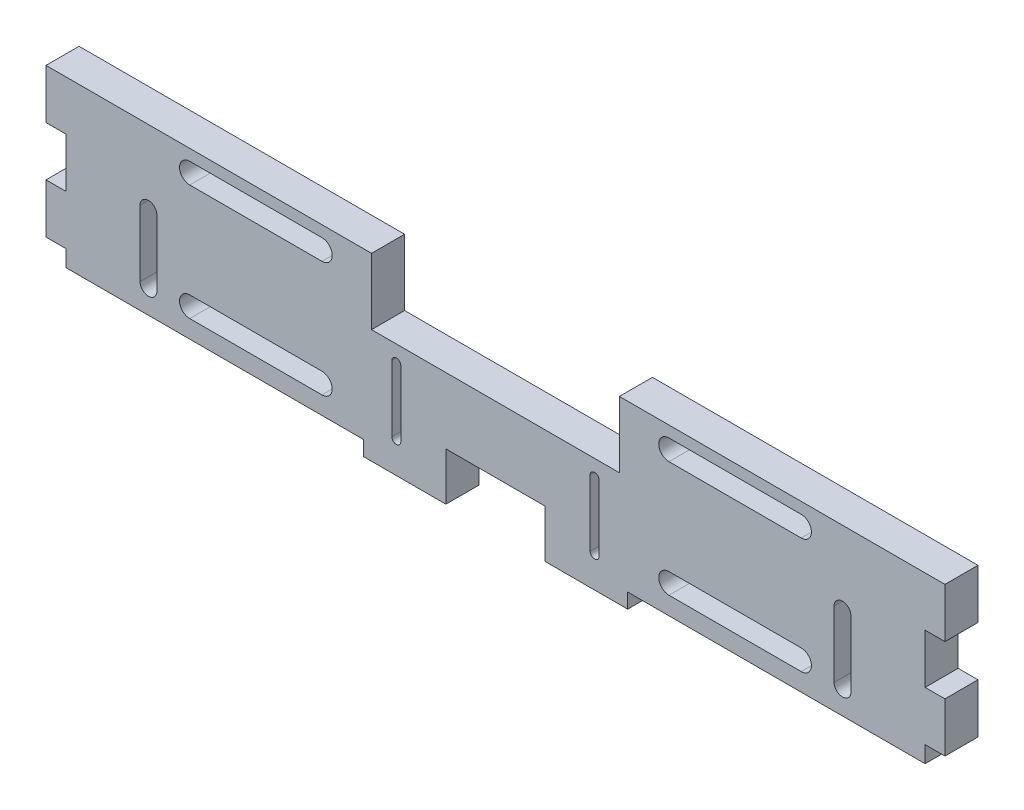
SolidWorks part; units mm, degrees
ref_plane "前基準面" through (0, 0, 0) normal (0, 0, 1) x (1, 0, 0)
ref_plane "上基準面" through (0, 0, 0) normal (0, 1, 0) x (1, 0, 0)
ref_plane "右基準面" through (0, 0, 0) normal (1, 0, 0) x (0, 0, -1)
sketch "草圖1" plane through (0, 0, 0) normal (0, 0, 1) x (1, 0, 0)
  line L0 (136, -22.5) -> (136, -7.5)
  line L1 (136, 22.5) -> (-136, 22.5)
  line L2 (130, 7.5) -> (130, -7.5)
  line L3 (130, -27.5) -> (-130, -27.5)
  line L4 (-130, 7.5) -> (-130, -7.5)
  line L5 (0, -27.5) -> (0, 22.5) construction
  line L6 (130, 0) -> (-130, 0) construction
  line L9 (-130, 7.5) -> (-136, 7.5)
  line L10 (-136, 22.5) -> (-136, 7.5)
  line L14 (-136, -22.5) -> (-136, -7.5)
  line L15 (130, -7.5) -> (136, -7.5)
  line L16 (130, 7.5) -> (136, 7.5)
  line L17 (136, 22.5) -> (136, 7.5)
  line L18 (-136, -22.5) -> (-130, -22.5)
  line L19 (-130, -22.5) -> (-130, -27.5)
  line L20 (-136, -7.5) -> (-130, -7.5)
  line L21 (130, -22.5) -> (130, -27.5)
  line L22 (130, -22.5) -> (136, -22.5)
  line L23 (-30, -22.5) -> (-30, -2.5) construction
  line L24 (-31.35, -22.5) -> (-31.35, -2.5)
  line L25 (-28.65, -22.5) -> (-28.65, -2.5)
  line L26 (30, -22.5) -> (30, -2.5) construction
  line L27 (31.35, -22.5) -> (31.35, -2.5)
  line L28 (28.65, -22.5) -> (28.65, -2.5)
  arc A0 (-31.35, -22.5) -> (-28.65, -22.5) centre (-30, -22.5) ccw
  arc A1 (-28.65, -2.5) -> (-31.35, -2.5) centre (-30, -2.5) ccw
  arc A2 (31.35, -22.5) -> (28.65, -22.5) centre (30, -22.5) cw
  arc A3 (28.65, -2.5) -> (31.35, -2.5) centre (30, -2.5) cw
  point P0 (0, 0)
  point P8 (0, 0)
  point P13 (-136, -15)
  point P14 (136, -15)
  point P24 (-30, -12.5)
  point P31 (30, -12.5)
  dimension "D8" = 1.35
  dimension "D1" = 260
  dimension "D2" = 6
  dimension "D3" = 15
  dimension "D4" = 6
  dimension "D5" = 50
  dimension "D6" = 5
  dimension "D7" = 20
  dimension "D9" = 5
  dimension "D10" = 30
extrude "填料-伸長1" add sketch "草圖1" along normal blind 10
sketch "草圖2" plane through (0, 0, 10) normal (0, 0, 1) x (1, 0, 0)
  line L0 (-92.5, 16) -> (-52.5, 16) construction
  line L1 (-92.5, 19.1) -> (-52.5, 19.1)
  line L2 (-92.5, 12.9) -> (-52.5, 12.9)
  line L3 (-92.5, -19) -> (-52.5, -19) construction
  line L4 (-92.5, -15.9) -> (-52.5, -15.9)
  line L5 (-92.5, -22.1) -> (-52.5, -22.1)
  line L6 (0, 61.8937) -> (0, -44.053) construction
  line L7 (-130, -27.5) -> (130, -27.5) construction
  line L8 (52.5, 16) -> (92.5, 16) construction
  line L9 (52.5, 19.1) -> (92.5, 19.1)
  line L10 (52.5, 12.9) -> (92.5, 12.9)
  line L11 (52.5, -19) -> (92.5, -19) construction
  line L12 (52.5, -15.9) -> (92.5, -15.9)
  line L13 (52.5, -22.1) -> (92.5, -22.1)
  arc A0 (-92.5, 19.1) -> (-92.5, 12.9) centre (-92.5, 16) ccw
  arc A1 (-52.5, 12.9) -> (-52.5, 19.1) centre (-52.5, 16) ccw
  arc A2 (-92.5, -15.9) -> (-92.5, -22.1) centre (-92.5, -19) ccw
  arc A3 (-52.5, -22.1) -> (-52.5, -15.9) centre (-52.5, -19) ccw
  arc A4 (52.5, 19.1) -> (52.5, 12.9) centre (52.5, 16) ccw
  arc A5 (92.5, 12.9) -> (92.5, 19.1) centre (92.5, 16) ccw
  arc A6 (52.5, -15.9) -> (52.5, -22.1) centre (52.5, -19) ccw
  arc A7 (92.5, -22.1) -> (92.5, -15.9) centre (92.5, -19) ccw
  point P2 (-72.5, 16)
  point P7 (-72.5, -19)
  point P22 (72.5, 16)
  point P27 (72.5, -19)
  point P37 (-95.6, -19)
  point P38 (49.4, -19)
  dimension "D3" = 3.1
  dimension "D1" = 35
  dimension "D2" = 5.4
  dimension "D4" = 40
  dimension "D6" = 145
  dimension "D5" = 2
extrude "除料-伸長1" cut sketch "草圖2" against normal through all
sketch "草圖3" plane through (0, 0, 10) normal (0, 0, 1) x (1, 0, 0)
  line L0 (0, 40.44) -> (0, -35.44) construction
  line L1 (-130, -27.5) -> (130, -27.5) construction
  line L2 (15, -17.5) -> (-15, -17.5)
  line L3 (15, -17.5) -> (15, -27.5)
  line L4 (15, -27.5) -> (-15, -27.5)
  line L5 (-15, -17.5) -> (-15, -27.5)
  line L6 (0, -27.5) -> (0, -17.5) construction
  line L7 (15, -22.5) -> (-15, -22.5) construction
  line L8 (136, 22.5) -> (-136, 22.5) construction
  line L9 (-37.5, 22.5) -> (37.5, 22.5)
  line L10 (-37.5, 22.5) -> (-37.5, 2.5)
  line L11 (-37.5, 2.5) -> (37.5, 2.5)
  line L12 (37.5, 22.5) -> (37.5, 2.5)
  line L13 (-105, 0.05) -> (-105, -19.95) construction
  line L14 (-102.45, 0.05) -> (-102.45, -19.95)
  line L15 (-107.55, 0.05) -> (-107.55, -19.95)
  line L16 (-130, 7.5) -> (-130, -7.5) construction
  line L17 (105, 0.05) -> (105, -19.95) construction
  line L18 (102.45, 0.05) -> (102.45, -19.95)
  line L19 (107.55, 0.05) -> (107.55, -19.95)
  circle A0 centre (0, 40.44) radius 36 construction
  arc A1 (-102.45, 0.05) -> (-107.55, 0.05) centre (-105, 0.05) ccw
  arc A2 (-107.55, -19.95) -> (-102.45, -19.95) centre (-105, -19.95) ccw
  arc A3 (102.45, 0.05) -> (107.55, 0.05) centre (105, 0.05) cw
  arc A4 (107.55, -19.95) -> (102.45, -19.95) centre (105, -19.95) cw
  point P3 (0, -22.5)
  point P16 (0, 2.5)
  point P22 (-105, -9.95)
  point P29 (-105, -22.5)
  point P33 (105, -9.95)
  dimension "D3" = 72
  dimension "D8" = 5.1
  dimension "D1" = 10
  dimension "D2" = 30
  dimension "D4" = 67.94
  dimension "D5" = 20
  dimension "D6" = 75
  dimension "D7" = 22.45
  dimension "D9" = 5
  dimension "D10" = 20
extrude "除料-伸長2" cut sketch "草圖3" against normal through all
sketch "草圖4" plane through (0, -27.5, 0) normal (0, -1, 0) x (1, 0, 0)
  line L0 (-130, 0) -> (-15, 0) construction
  line L1 (-15, 10) -> (-40, 10)
  line L2 (-15, 10) -> (-15, 0)
  line L3 (-15, 0) -> (-40, 0)
  line L4 (-40, 10) -> (-40, 0)
  line L5 (0, 39.3448) -> (0, -9.8344) construction
  line L6 (15, 0) -> (40, 0)
  line L7 (40, 10) -> (40, 0)
  line L8 (15, 10) -> (40, 10)
  line L9 (15, 10) -> (15, 0)
  dimension "D1" = 25
  dimension "D2" = 30
extrude "填料-伸長2" add sketch "草圖4" along normal blind 4.5
